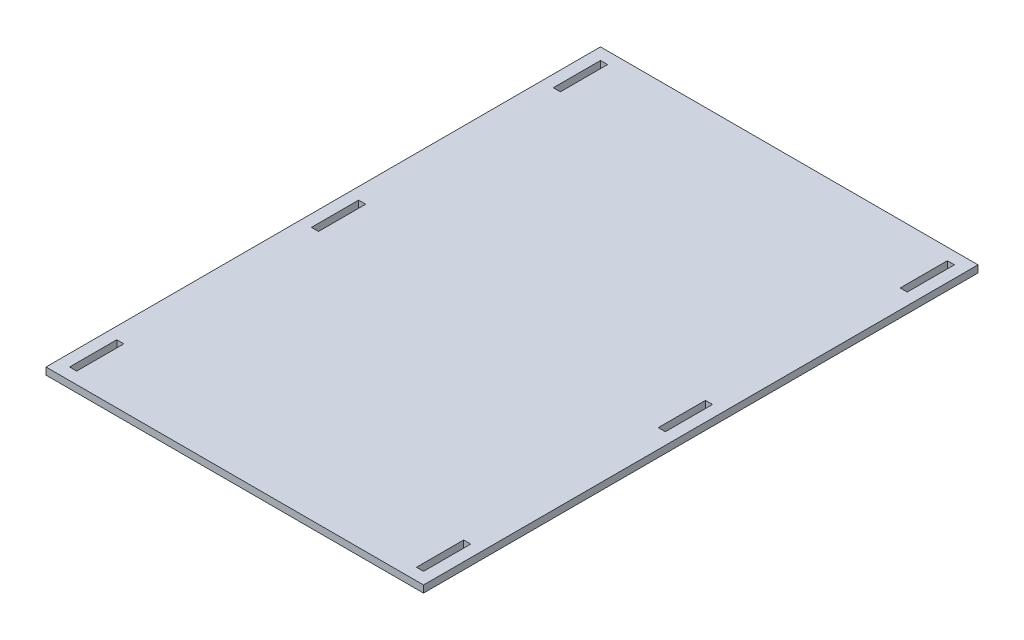
SolidWorks part; units mm, degrees
ref_plane "Front Plane" through (0, 0, 0) normal (0, 0, 1) x (1, 0, 0)
ref_plane "Top Plane" through (0, 0, 0) normal (0, 1, 0) x (1, 0, 0)
ref_plane "Right Plane" through (0, 0, 0) normal (1, 0, 0) x (0, 0, -1)
sketch "Sketch1" plane through (0, 0, 0) normal (0, 1, 0) x (1, 0, 0)
  line L1 (0, 0) -> (320, 0)
  line L2 (0, 0) -> (0, 470)
  line L3 (0, 470) -> (320, 470)
  line L4 (320, 0) -> (320, 470)
  dimension "D1" = 470
  dimension "D2" = 320
extrude "Boss-Extrude1" add sketch "Sketch1" along normal blind 6 contours L2 L3 L4 L1
sketch "Sketch2" plane through (0, 6, 0) normal (0, 1, 0) x (1, 0, 0)
  line L1 (10, 460) -> (16, 460)
  line L2 (10, 460) -> (10, 420)
  line L3 (10, 420) -> (16, 420)
  line L4 (16, 460) -> (16, 420)
  line L5 (0, 0) -> (0, 470) construction
  line L7 (0, 470) -> (320, 470) construction
  dimension "D1" = 40
  dimension "D2" = 6
  dimension "D3" = 10
  dimension "D4" = 10
extrude "Cut-Extrude1" cut sketch "Sketch2" against normal blind 6
pattern_linear "LPattern1" count 2 spacing 294 along (1, 0, 0) count 3 spacing 205 along (0, 0, 1) of "Cut-Extrude1"
